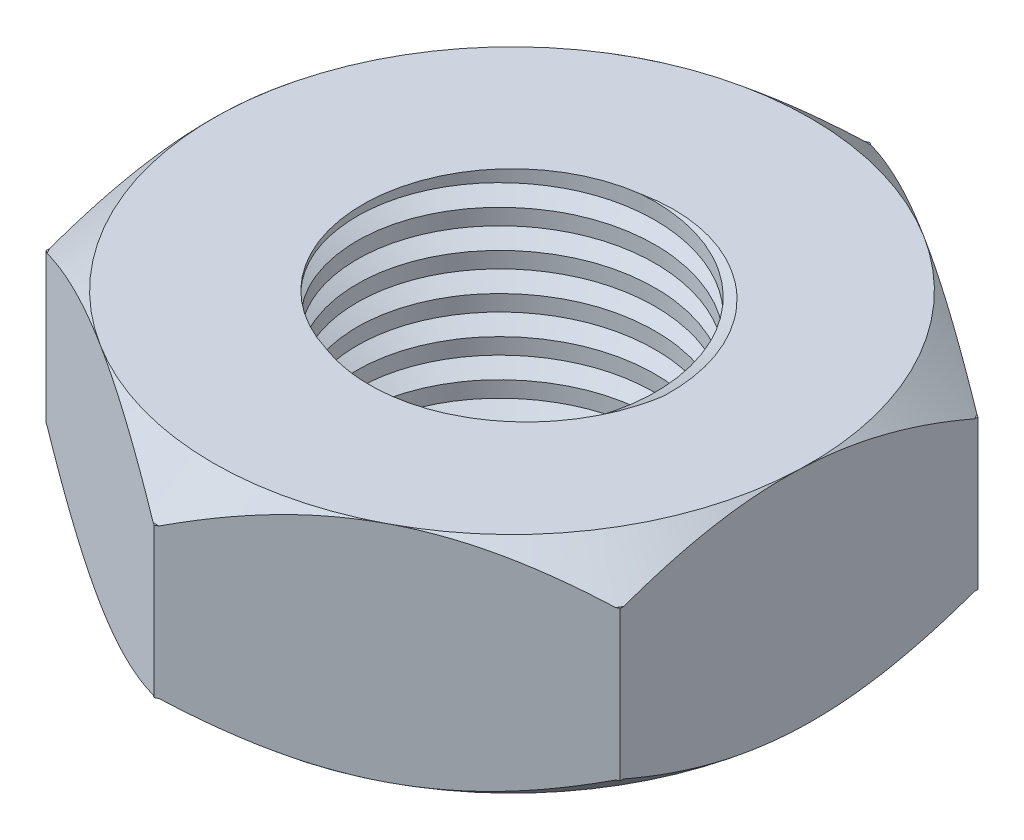
SolidWorks part; units mm, degrees
ref_plane "Front Plane" through (0, 0, 0) normal (0, 0, 1) x (1, 0, 0)
ref_plane "Top Plane" through (0, 0, 0) normal (0, 1, 0) x (1, 0, 0)
ref_plane "Right Plane" through (0, 0, 0) normal (1, 0, 0) x (0, 0, -1)
sketch "Sketch1" plane through (0, 0, 0) normal (0, 1, 0) x (1, 0, 0)
  line L1 (2.0425, 1.0778) -> (0.0878, 2.3077)
  line L2 (0.0878, 2.3077) -> (-1.9546, 1.2299)
  line L3 (-1.9546, 1.2299) -> (-2.0425, -1.0778)
  line L4 (-2.0425, -1.0778) -> (-0.0878, -2.3077)
  line L5 (-0.0878, -2.3077) -> (1.9546, -1.2299)
  line L6 (1.9546, -1.2299) -> (2.0425, 1.0778)
  circle A0 centre (0, 0) radius 2 construction
  circle A1 centre (0, 0) radius 1
extrude "Boss-Extrude2" add sketch "Sketch1" along normal blind 1.5
sketch "Sketch3" plane through (0, 1.5, 0) normal (0, 1, 0) x (1, 0, 0)
  circle A0 centre (0, 0) radius 2
extrude "Cut-Extrude2" cut sketch "Sketch3" against normal blind 0.25 draft 50 flip side to cut
sketch "Sketch4" plane through (0, 0, 0) normal (0, -1, 0) x (1, 0, 0)
  circle A0 centre (0, 0) radius 2
extrude "Cut-Extrude3" cut sketch "Sketch4" against normal blind 0.25 draft 50 flip side to cut
sketch "Sketch5" plane through (0, 1.5, 0) normal (0, 1, 0) x (1, 0, 0)
  circle A0 centre (0, 0) radius 1
curve "Helix/Spiral1" pitch 0.25 height 2 turns 8
sketch "Sketch6" plane through (0, 0, 0) normal (0, 0, 1) x (1, 0, 0)
  line L1 (1.1235, -0.4967) -> (0.933, -0.3867)
  line L2 (0.933, -0.3867) -> (0.933, -0.6067)
  line L3 (0.933, -0.6067) -> (1.1235, -0.4967)
  circle A0 centre (0.9965, -0.4967) radius 0.0635 construction
  spline S0 degree 3 poles (1, 1.5) (1, 1.4948) (0.9479, 1.4844) (0.7255, 1.4688) (0.3926, 1.4531) (0, 1.4375) (-0.3926, 1.4219) (-0.7255, 1.4063) (-0.9479, 1.3906) (-1.026, 1.375) (-0.9479, 1.3594) (-0.7255, 1.3438) (-0.3926, 1.3281) (0, 1.3125) (0.3926, 1.2969) (0.7255, 1.2813) (0.9479, 1.2656) (1.026, 1.25) (0.9479, 1.2344) (0.7255, 1.2188) (0.3926, 1.2031) (0, 1.1875) (-0.3926, 1.1719) (-0.7255, 1.1562) (-0.9479, 1.1406) (-1.026, 1.125) (-0.9479, 1.1094) (-0.7255, 1.0937) (-0.3926, 1.0781) (0, 1.0625) (0.3926, 1.0469) (0.7255, 1.0312) (0.9479, 1.0156) (1.026, 1) (0.9479, 0.9844) (0.7255, 0.9688) (0.3926, 0.9531) (0, 0.9375) (-0.3926, 0.9219) (-0.7255, 0.9062) (-0.9479, 0.8906) (-1.026, 0.875) (-0.9479, 0.8594) (-0.7255, 0.8437) (-0.3926, 0.8281) (0, 0.8125) (0.3926, 0.7969) (0.7255, 0.7812) (0.9479, 0.7656) (1.026, 0.75) (0.9479, 0.7344) (0.7255, 0.7187) (0.3926, 0.7031) (0, 0.6875) (-0.3926, 0.6719) (-0.7255, 0.6562) (-0.9479, 0.6406) (-1.026, 0.625) (-0.9479, 0.6094) (-0.7255, 0.5937) (-0.3926, 0.5781) (0, 0.5625) (0.3926, 0.5469) (0.7255, 0.5312) (0.9479, 0.5156) (1.026, 0.5) (0.9479, 0.4844) (0.7255, 0.4687) (0.3926, 0.4531) (0, 0.4375) (-0.3926, 0.4219) (-0.7255, 0.4062) (-0.9479, 0.3906) (-1.026, 0.375) (-0.9479, 0.3594) (-0.7255, 0.3437) (-0.3926, 0.3281) (0, 0.3125) (0.3926, 0.2969) (0.7255, 0.2812) (0.9479, 0.2656) (1.026, 0.25) (0.9479, 0.2344) (0.7255, 0.2187) (0.3926, 0.2031) (0, 0.1875) (-0.3926, 0.1719) (-0.7255, 0.1562) (-0.9479, 0.1406) (-1.026, 0.125) (-0.9479, 0.1094) (-0.7255, 0.0937) (-0.3926, 0.0781) (0, 0.0625) (0.3926, 0.0469) (0.7255, 0.0312) (0.9479, 0.0156) (1.026, 0) (0.9479, -0.0156) (0.7255, -0.0313) (0.3926, -0.0469) (0, -0.0625) (-0.3926, -0.0781) (-0.7255, -0.0938) (-0.9479, -0.1094) (-1.026, -0.125) (-0.9479, -0.1406) (-0.7255, -0.1563) (-0.3926, -0.1719) (0, -0.1875) (0.3926, -0.2031) (0.7255, -0.2188) (0.9479, -0.2344) (1.026, -0.25) (0.9479, -0.2656) (0.7255, -0.2813) (0.3926, -0.2969) (0, -0.3125) (-0.3926, -0.3281) (-0.7255, -0.3438) (-0.9479, -0.3594) (-1.026, -0.375) (-0.9479, -0.3906) (-0.7255, -0.4063) (-0.3926, -0.4219) (0, -0.4375) (0.3926, -0.4531) (0.7255, -0.4688) (0.9479, -0.4844) (1, -0.4948) (1, -0.5) knots 0 0 0 0 0.007813 0.015625 0.023438 0.03125 0.039063 0.046875 0.054688 0.0625 0.070313 0.078125 0.085938 0.09375 0.101563 0.109375 0.117188 0.125 0.132813 0.140625 0.148438 0.15625 0.164063 0.171875 0.179688 0.1875 0.195312 0.203125 0.210937 0.21875 0.226562 0.234375 0.242187 0.25 0.257812 0.265625 0.273437 0.28125 0.289062 0.296875 0.304687 0.3125 0.320312 0.328125 0.335938 0.34375 0.351563 0.359375 0.367188 0.375 0.382812 0.390625 0.398437 0.40625 0.414062 0.421875 0.429687 0.4375 0.445312 0.453125 0.460937 0.46875 0.476562 0.484375 0.492187 0.5 0.507812 0.515625 0.523437 0.53125 0.539062 0.546875 0.554687 0.5625 0.570312 0.578125 0.585937 0.59375 0.601562 0.609375 0.617187 0.625 0.632812 0.640625 0.648437 0.65625 0.664062 0.671875 0.679687 0.6875 0.695312 0.703125 0.710937 0.71875 0.726562 0.734375 0.742187 0.75 0.757812 0.765625 0.773437 0.78125 0.789062 0.796875 0.804687 0.8125 0.820312 0.828125 0.835937 0.84375 0.851562 0.859375 0.867187 0.875 0.882812 0.890625 0.898437 0.90625 0.914062 0.921875 0.929687 0.9375 0.945312 0.953125 0.960937 0.96875 0.976562 0.984375 0.992187 1 1 1 1 construction
  dimension "D1" = 0.22
sweep "Cut-Sweep1" cut profiles "Sketch6" path "Helix/Spiral1"
